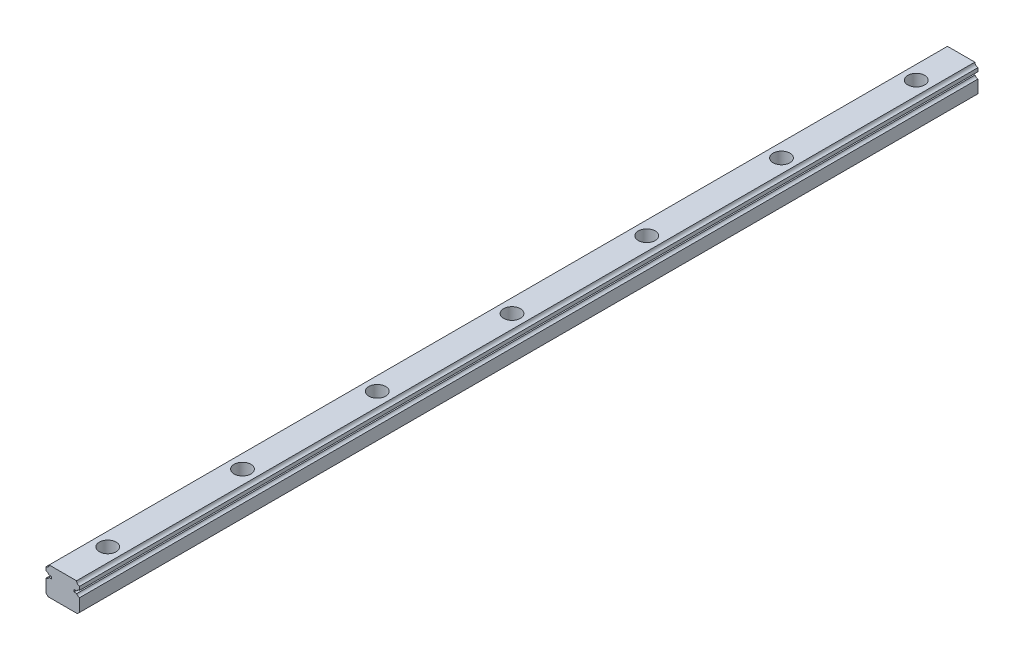
SolidWorks part; units mm, degrees
ref_plane "Front" through (0, 0, 0) normal (0, 0, 1) x (1, 0, 0)
ref_plane "Top" through (0, 0, 0) normal (0, 1, 0) x (1, 0, 0)
ref_plane "Right" through (0, 0, 0) normal (1, 0, 0) x (0, 0, -1)
sketch "15mm" plane through (0, 0, 0) normal (0, 0, 1) x (1, 0, 0)
  line L0 (0, 0) -> (0, 12.5) construction
  line L2 (4.95, 7.6) -> (6.1923, 7.6)
  line L3 (4.95, 8.6) -> (4.95, 7.6)
  line L4 (6.1923, 8.6) -> (4.95, 8.6)
  line L5 (7.5, 11.1) -> (7.5, 9.5)
  line L6 (-6.1, 12.5) -> (6.1, 12.5)
  line L7 (-7.5, 9.5) -> (-7.5, 11.1)
  line L8 (-4.95, 8.6) -> (-6.1923, 8.6)
  line L9 (-4.95, 7.6) -> (-4.95, 8.6)
  line L10 (-6.1923, 7.6) -> (-4.95, 7.6)
  line L11 (-7.5, 1) -> (-7.5, 6.7)
  line L12 (-6.5, 0) -> (-7.5, 1)
  line L13 (6.5, 0) -> (-6.5, 0)
  line L14 (7.5, 1) -> (6.5, 0)
  line L15 (7.5, 6.7) -> (7.5, 1)
  arc A0 (6.1923, 8.6) -> (7.5, 9.5) centre (7.5, 8.1) cw
  arc A1 (7.5, 11.1) -> (6.1, 12.5) centre (7.5, 12.5) cw
  arc A2 (-6.1, 12.5) -> (-7.5, 11.1) centre (-7.5, 12.5) cw
  arc A3 (-7.5, 9.5) -> (-6.1923, 8.6) centre (-7.5, 8.1) cw
  arc A4 (-6.1923, 7.6) -> (-7.5, 6.7) centre (-7.5, 8.1) cw
  arc A5 (7.5, 6.7) -> (6.1923, 7.6) centre (7.5, 8.1) cw
extrude "Extrude1" add sketch "15mm" along normal mid plane 400
sketch "Sketch1" plane through (0, 0, 0) normal (1, 0, 0) x (0, 0, -1)
  line L0 (-180, 0) -> (-180, 12.5) construction
  line L1 (-200, 0) -> (200, 0) construction
  line L2 (-200, 12.5) -> (200, 12.5) construction
  line L3 (-180, 12.5) -> (-176.25, 12.5)
  line L4 (-176.25, 12.5) -> (-176.25, 7.2)
  line L5 (-176.25, 7.2) -> (-177.75, 7.2)
  line L6 (-177.75, 7.2) -> (-177.75, 0)
  line L7 (-177.75, 0) -> (-180, 0)
  line L8 (-180, 0) -> (-180, 12.5)
  line L9 (-200, 1) -> (-200, 6.7) construction
  dimension "D1" = 4.5
  dimension "D2" = 7.5
  dimension "D3" = 5.3
  dimension "D4" = 20
revolve "Cut-Revolve1" cut sketch "Sketch1" angle 360 about L0
sketch "Sketch2" plane through (0, 0, 0) normal (1, 0, 0) x (0, 0, -1)
  line L0 (180, 12.5) -> (180, 0) construction
  line L1 (-200, 12.5) -> (200, 12.5) construction
  line L2 (-200, 0) -> (200, 0) construction
  line L3 (180, 0) -> (182.25, 0)
  line L4 (182.25, 0) -> (182.25, 7.2)
  line L5 (182.25, 7.2) -> (183.75, 7.2)
  line L6 (183.75, 7.2) -> (183.75, 12.5)
  line L7 (183.75, 12.5) -> (180, 12.5)
  line L8 (180, 0) -> (200, 0) construction
  line L9 (-177.75, 0) -> (-180, 0) construction
  line L10 (-180, 12.5) -> (-176.25, 12.5) construction
  line L11 (-200, 0) -> (-180, 0) construction
  line L12 (-176.25, 7.2) -> (-177.75, 7.2) construction
  line L13 (180, 12.5) -> (180, 0)
revolve "Cut-Revolve2" cut sketch "Sketch2" angle 360 about L0
ref_axis "Axis1" through (0, 0, -121) along (0, 0, 1)
pattern_linear "LPattern1" count 6 spacing 60 along (0, 0, 1) of "Cut-Revolve2"
